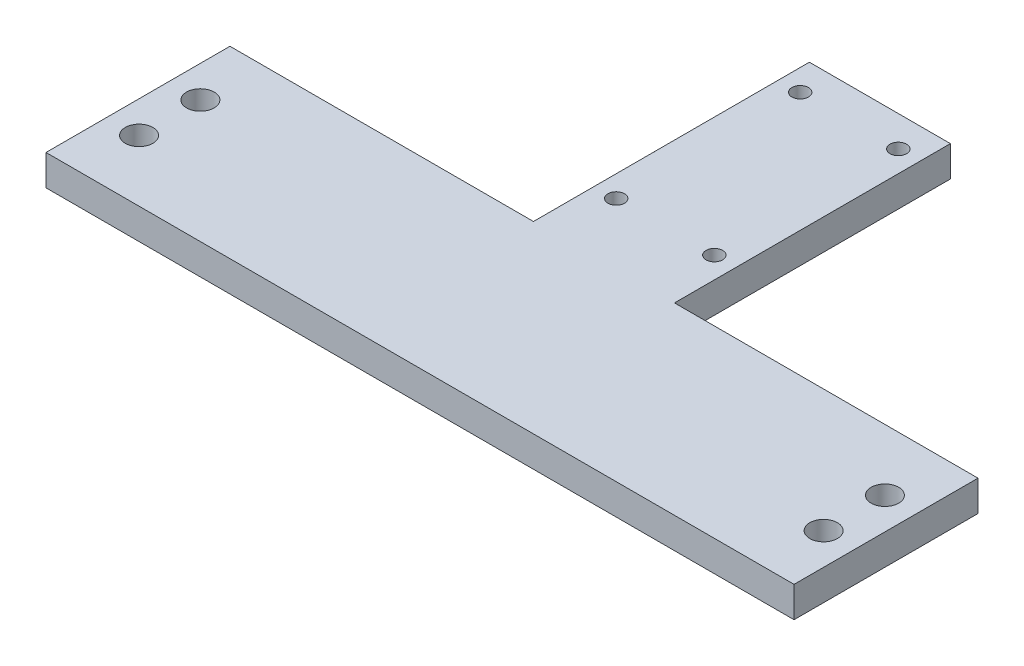
SolidWorks part; units mm, degrees
ref_plane "Front Plane" through (0, 0, 0) normal (0, 0, 1) x (1, 0, 0)
ref_plane "Top Plane" through (0, 0, 0) normal (0, 1, 0) x (1, 0, 0)
ref_plane "Right Plane" through (0, 0, 0) normal (1, 0, 0) x (0, 0, -1)
sketch "Sketch1" plane through (0, 0, 0) normal (0, 1, 0) x (1, 0, 0)
  line L1 (-61, 15) -> (61, 15)
  line L2 (-61, 15) -> (-61, -15)
  line L3 (-61, -15) -> (61, -15)
  line L4 (61, 15) -> (61, -15)
  line L5 (-61, 15) -> (61, -15) construction
  line L6 (-61, -15) -> (61, 15) construction
  point P0 (0, 0)
  dimension "D1" = 122
  dimension "D2" = 30
extrude "Boss-Extrude1" add sketch "Sketch1" along normal blind 5
sketch "Sketch2" plane through (0, 0, 0) normal (0, 1, 0) x (1, 0, 0)
  line L0 (61, 15) -> (-61, 15) construction
  line L1 (-11.5, 15) -> (11.5, 15)
  line L2 (-11.5, 15) -> (-11.5, 60)
  line L3 (-11.5, 60) -> (11.5, 60)
  line L4 (11.5, 15) -> (11.5, 60)
  line L6 (-61, 15) -> (-61, -15) construction
  dimension "D1" = 45
  dimension "D2" = 23
  dimension "D3" = 49.5
extrude "Boss-Extrude2" add sketch "Sketch2" along normal blind 5
sketch "Sketch4" plane through (0, 5, 0) normal (0, 1, 0) x (1, 0, 0)
  line L0 (-11.5, 15) -> (-61, 15) construction
  line L1 (0, -55) -> (0, 55) construction
  circle A0 centre (-55.822, 5) radius 2.25
  circle A1 centre (-55.822, -5) radius 2.25
  circle A2 centre (55.822, -5) radius 2.25
  circle A3 centre (55.822, 5) radius 2.25
  dimension "D3" = 4.5
  dimension "D4" = 4.5
  dimension "D1" = 10
  dimension "D2" = 10
extrude "Cut-Extrude2" cut sketch "Sketch4" against normal through all
sketch "Sketch6" plane through (0, 5, 0) normal (0, 1, 0) x (1, 0, 0)
  line L0 (0, -2.75) -> (0, 2.75) construction
  line L1 (-11.5, 15) -> (-61, 15) construction
  circle A0 centre (-8, 55) radius 1.35
  circle A1 centre (-8, 25) radius 1.35
  circle A2 centre (8, 25) radius 1.35
  circle A3 centre (8, 55) radius 1.35
  point P6 (0, 0)
  point P7 (0, 0)
  point P12 (0, 0)
  dimension "D2" = 2.7
  dimension "D4" = 2.7
  dimension "D1" = 8
  dimension "D3" = 30
  dimension "D5" = 40
extrude "Cut-Extrude3" cut sketch "Sketch6" against normal through all
equation "\"D3@Sketch2\"=(122-23)/2"
equation "\"D4@Sketch6\"=\"D2@Sketch6\""
